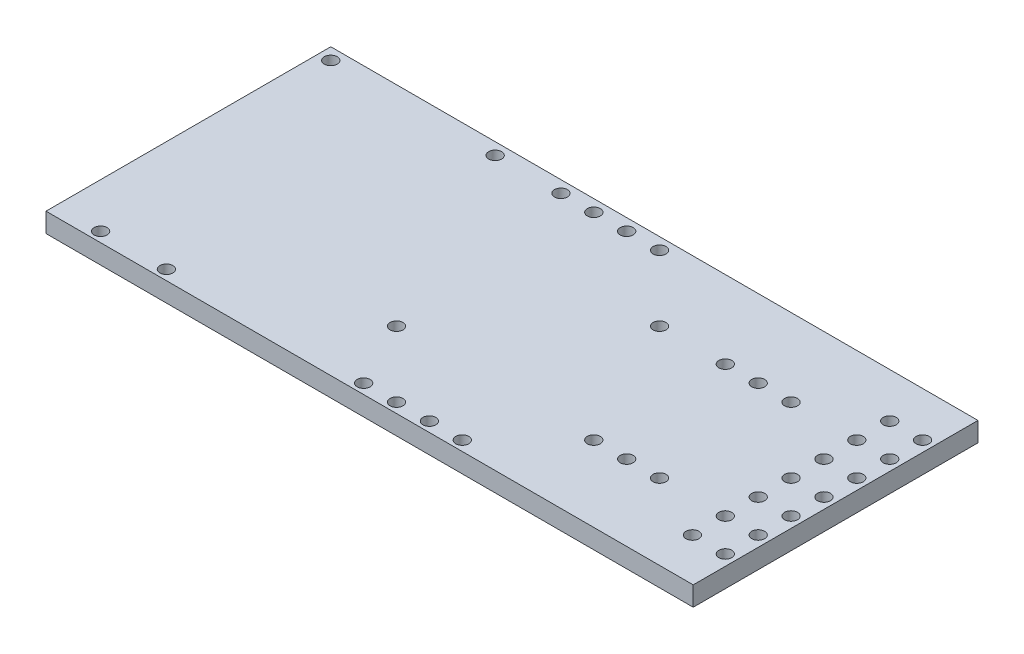
SolidWorks part; units mm, degrees
material "Chrome Stainless Steel"
ref_plane "Front Plane" through (0, 0, 0) normal (0, 0, 1) x (1, 0, 0)
ref_plane "Top Plane" through (0, 0, 0) normal (0, 1, 0) x (1, 0, 0)
ref_plane "Right Plane" through (0, 0, 0) normal (1, 0, 0) x (0, 0, -1)
sketch "Sketch1" plane through (0, 0, 0) normal (0, 1, 0) x (1, 0, 0)
  line L0 (0, 0) -> (2.54, 0) construction
  line L1 (-5.75, 3.5) -> (64.25, 3.5)
  line L2 (-5.75, 3.5) -> (-5.75, -26.5)
  line L3 (-5.75, -26.5) -> (64.25, -26.5)
  line L4 (64.25, 3.5) -> (64.25, -26.5)
  line L5 (0, 0) -> (0, -2.54) construction
  circle A0 centre (0, 0) radius 0.5 construction
  circle A1 centre (2.54, 0) radius 0.5 construction
  circle A2 centre (5.08, 0) radius 0.5 construction
  circle A3 centre (7.62, 0) radius 0.5 construction
  circle A4 centre (10.16, 0) radius 0.5 construction
  circle A5 centre (12.7, 0) radius 0.5 construction
  circle A6 centre (15.24, 0) radius 0.5 construction
  circle A7 centre (17.78, 0) radius 0.5 construction
  circle A8 centre (20.32, 0) radius 0.5 construction
  circle A9 centre (22.86, 0) radius 0.5 construction
  circle A10 centre (25.4, 0) radius 0.5 construction
  circle A11 centre (27.94, 0) radius 0.5 construction
  circle A12 centre (30.48, 0) radius 0.5 construction
  circle A13 centre (33.02, 0) radius 0.5 construction
  circle A14 centre (35.56, 0) radius 0.5 construction
  circle A15 centre (38.1, 0) radius 0.5 construction
  circle A16 centre (40.64, 0) radius 0.5 construction
  circle A17 centre (43.18, 0) radius 0.5 construction
  circle A18 centre (45.72, 0) radius 0.5 construction
  circle A19 centre (48.26, 0) radius 0.5 construction
  circle A20 centre (50.8, 0) radius 0.5 construction
  circle A21 centre (53.34, 0) radius 0.5 construction
  circle A22 centre (55.88, 0) radius 0.5 construction
  circle A23 centre (58.42, 0) radius 0.5 construction
  circle A24 centre (2.54, -2.54) radius 0.5 construction
  circle A25 centre (5.08, -2.54) radius 0.5 construction
  circle A26 centre (7.62, -2.54) radius 0.5 construction
  circle A27 centre (10.16, -2.54) radius 0.5 construction
  circle A28 centre (12.7, -2.54) radius 0.5
  circle A29 centre (15.24, -2.54) radius 0.5 construction
  circle A30 centre (17.78, -2.54) radius 0.5
  circle A31 centre (20.32, -2.54) radius 0.5
  circle A32 centre (22.86, -2.54) radius 0.5
  circle A33 centre (25.4, -2.54) radius 0.5
  circle A34 centre (27.94, -2.54) radius 0.5 construction
  circle A35 centre (30.48, -2.54) radius 0.5 construction
  circle A36 centre (33.02, -2.54) radius 0.5 construction
  circle A37 centre (35.56, -2.54) radius 0.5 construction
  circle A38 centre (38.1, -2.54) radius 0.5 construction
  circle A39 centre (40.64, -2.54) radius 0.5 construction
  circle A40 centre (43.18, -2.54) radius 0.5 construction
  circle A41 centre (45.72, -2.54) radius 0.5 construction
  circle A42 centre (48.26, -2.54) radius 0.5 construction
  circle A43 centre (50.8, -2.54) radius 0.5 construction
  circle A44 centre (53.34, -2.54) radius 0.5 construction
  circle A45 centre (55.88, -2.54) radius 0.5 construction
  circle A46 centre (58.42, -2.54) radius 0.5 construction
  circle A47 centre (2.54, -5.08) radius 0.5 construction
  circle A48 centre (5.08, -5.08) radius 0.5 construction
  circle A49 centre (7.62, -5.08) radius 0.5 construction
  circle A50 centre (10.16, -5.08) radius 0.5 construction
  circle A51 centre (12.7, -5.08) radius 0.5 construction
  circle A52 centre (15.24, -5.08) radius 0.5 construction
  circle A53 centre (17.78, -5.08) radius 0.5 construction
  circle A54 centre (20.32, -5.08) radius 0.5 construction
  circle A55 centre (22.86, -5.08) radius 0.5 construction
  circle A56 centre (25.4, -5.08) radius 0.5 construction
  circle A57 centre (27.94, -5.08) radius 0.5 construction
  circle A58 centre (30.48, -5.08) radius 0.5 construction
  circle A59 centre (33.02, -5.08) radius 0.5 construction
  circle A60 centre (35.56, -5.08) radius 0.5 construction
  circle A61 centre (38.1, -5.08) radius 0.5 construction
  circle A62 centre (40.64, -5.08) radius 0.5 construction
  circle A63 centre (43.18, -5.08) radius 0.5 construction
  circle A64 centre (45.72, -5.08) radius 0.5
  circle A65 centre (48.26, -5.08) radius 0.5
  circle A66 centre (50.8, -5.08) radius 0.5 construction
  circle A67 centre (53.34, -5.08) radius 0.5 construction
  circle A68 centre (55.88, -5.08) radius 0.5 construction
  circle A69 centre (58.42, -5.08) radius 0.5 construction
  circle A70 centre (2.54, -7.62) radius 0.5 construction
  circle A71 centre (5.08, -7.62) radius 0.5 construction
  circle A72 centre (7.62, -7.62) radius 0.5 construction
  circle A73 centre (10.16, -7.62) radius 0.5 construction
  circle A74 centre (12.7, -7.62) radius 0.5 construction
  circle A75 centre (15.24, -7.62) radius 0.5 construction
  circle A76 centre (17.78, -7.62) radius 0.5 construction
  circle A77 centre (20.32, -7.62) radius 0.5 construction
  circle A78 centre (22.86, -7.62) radius 0.5 construction
  circle A79 centre (25.4, -7.62) radius 0.5 construction
  circle A80 centre (27.94, -7.62) radius 0.5 construction
  circle A81 centre (30.48, -7.62) radius 0.5
  circle A82 centre (33.02, -7.62) radius 0.5 construction
  circle A83 centre (35.56, -7.62) radius 0.5
  circle A84 centre (38.1, -7.62) radius 0.5
  circle A85 centre (40.64, -7.62) radius 0.5
  circle A86 centre (43.18, -7.62) radius 0.5 construction
  circle A87 centre (45.72, -7.62) radius 0.5
  circle A88 centre (48.26, -7.62) radius 0.5
  circle A89 centre (50.8, -7.62) radius 0.5 construction
  circle A90 centre (53.34, -7.62) radius 0.5 construction
  circle A91 centre (55.88, -7.62) radius 0.5 construction
  circle A92 centre (58.42, -7.62) radius 0.5 construction
  circle A93 centre (2.54, -10.16) radius 0.5 construction
  circle A94 centre (5.08, -10.16) radius 0.5 construction
  circle A95 centre (7.62, -10.16) radius 0.5 construction
  circle A96 centre (10.16, -10.16) radius 0.5 construction
  circle A97 centre (12.7, -10.16) radius 0.5 construction
  circle A98 centre (15.24, -10.16) radius 0.5 construction
  circle A99 centre (17.78, -10.16) radius 0.5 construction
  circle A100 centre (20.32, -10.16) radius 0.5 construction
  circle A101 centre (22.86, -10.16) radius 0.5 construction
  circle A102 centre (25.4, -10.16) radius 0.5 construction
  circle A103 centre (27.94, -10.16) radius 0.5 construction
  circle A104 centre (30.48, -10.16) radius 0.5 construction
  circle A105 centre (33.02, -10.16) radius 0.5 construction
  circle A106 centre (35.56, -10.16) radius 0.5 construction
  circle A107 centre (38.1, -10.16) radius 0.5 construction
  circle A108 centre (40.64, -10.16) radius 0.5 construction
  circle A109 centre (43.18, -10.16) radius 0.5 construction
  circle A110 centre (45.72, -10.16) radius 0.5
  circle A111 centre (48.26, -10.16) radius 0.5
  circle A112 centre (50.8, -10.16) radius 0.5 construction
  circle A113 centre (53.34, -10.16) radius 0.5 construction
  circle A114 centre (55.88, -10.16) radius 0.5 construction
  circle A115 centre (58.42, -10.16) radius 0.5 construction
  circle A116 centre (2.54, -12.7) radius 0.5 construction
  circle A117 centre (5.08, -12.7) radius 0.5 construction
  circle A118 centre (7.62, -12.7) radius 0.5 construction
  circle A119 centre (10.16, -12.7) radius 0.5 construction
  circle A120 centre (12.7, -12.7) radius 0.5 construction
  circle A121 centre (15.24, -12.7) radius 0.5 construction
  circle A122 centre (17.78, -12.7) radius 0.5 construction
  circle A123 centre (20.32, -12.7) radius 0.5 construction
  circle A124 centre (22.86, -12.7) radius 0.5 construction
  circle A125 centre (25.4, -12.7) radius 0.5 construction
  circle A126 centre (27.94, -12.7) radius 0.5 construction
  circle A127 centre (30.48, -12.7) radius 0.5 construction
  circle A128 centre (33.02, -12.7) radius 0.5 construction
  circle A129 centre (35.56, -12.7) radius 0.5 construction
  circle A130 centre (38.1, -12.7) radius 0.5 construction
  circle A131 centre (40.64, -12.7) radius 0.5 construction
  circle A132 centre (43.18, -12.7) radius 0.5 construction
  circle A133 centre (45.72, -12.7) radius 0.5
  circle A134 centre (48.26, -12.7) radius 0.5
  circle A135 centre (50.8, -12.7) radius 0.5 construction
  circle A136 centre (53.34, -12.7) radius 0.5 construction
  circle A137 centre (55.88, -12.7) radius 0.5 construction
  circle A138 centre (58.42, -12.7) radius 0.5 construction
  circle A139 centre (2.54, -15.24) radius 0.5 construction
  circle A140 centre (5.08, -15.24) radius 0.5 construction
  circle A141 centre (7.62, -15.24) radius 0.5 construction
  circle A142 centre (10.16, -15.24) radius 0.5 construction
  circle A143 centre (12.7, -15.24) radius 0.5 construction
  circle A144 centre (15.24, -15.24) radius 0.5 construction
  circle A145 centre (17.78, -15.24) radius 0.5 construction
  circle A146 centre (20.32, -15.24) radius 0.5 construction
  circle A147 centre (22.86, -15.24) radius 0.5 construction
  circle A148 centre (25.4, -15.24) radius 0.5 construction
  circle A149 centre (27.94, -15.24) radius 0.5 construction
  circle A150 centre (30.48, -15.24) radius 0.5 construction
  circle A151 centre (33.02, -15.24) radius 0.5 construction
  circle A152 centre (35.56, -15.24) radius 0.5 construction
  circle A153 centre (38.1, -15.24) radius 0.5 construction
  circle A154 centre (40.64, -15.24) radius 0.5 construction
  circle A155 centre (43.18, -15.24) radius 0.5 construction
  circle A156 centre (45.72, -15.24) radius 0.5
  circle A157 centre (48.26, -15.24) radius 0.5
  circle A158 centre (50.8, -15.24) radius 0.5 construction
  circle A159 centre (53.34, -15.24) radius 0.5 construction
  circle A160 centre (55.88, -15.24) radius 0.5 construction
  circle A161 centre (58.42, -15.24) radius 0.5 construction
  circle A162 centre (2.54, -17.78) radius 0.5 construction
  circle A163 centre (5.08, -17.78) radius 0.5 construction
  circle A164 centre (7.62, -17.78) radius 0.5 construction
  circle A165 centre (10.16, -17.78) radius 0.5 construction
  circle A166 centre (12.7, -17.78) radius 0.5 construction
  circle A167 centre (15.24, -17.78) radius 0.5 construction
  circle A168 centre (17.78, -17.78) radius 0.5 construction
  circle A169 centre (20.32, -17.78) radius 0.5
  circle A170 centre (22.86, -17.78) radius 0.5 construction
  circle A171 centre (25.4, -17.78) radius 0.5 construction
  circle A172 centre (27.94, -17.78) radius 0.5 construction
  circle A173 centre (30.48, -17.78) radius 0.5 construction
  circle A174 centre (33.02, -17.78) radius 0.5 construction
  circle A175 centre (35.56, -17.78) radius 0.5
  circle A176 centre (38.1, -17.78) radius 0.5
  circle A177 centre (40.64, -17.78) radius 0.5
  circle A178 centre (43.18, -17.78) radius 0.5 construction
  circle A179 centre (45.72, -17.78) radius 0.5
  circle A180 centre (48.26, -17.78) radius 0.5
  circle A181 centre (50.8, -17.78) radius 0.5 construction
  circle A182 centre (53.34, -17.78) radius 0.5 construction
  circle A183 centre (55.88, -17.78) radius 0.5 construction
  circle A184 centre (58.42, -17.78) radius 0.5 construction
  circle A185 centre (2.54, -20.32) radius 0.5 construction
  circle A186 centre (5.08, -20.32) radius 0.5 construction
  circle A187 centre (7.62, -20.32) radius 0.5 construction
  circle A188 centre (10.16, -20.32) radius 0.5 construction
  circle A189 centre (12.7, -20.32) radius 0.5 construction
  circle A190 centre (15.24, -20.32) radius 0.5 construction
  circle A191 centre (17.78, -20.32) radius 0.5 construction
  circle A192 centre (20.32, -20.32) radius 0.5 construction
  circle A193 centre (62.25, 1.5) radius 1
  circle A194 centre (62.25, -24.5) radius 1
  circle A195 centre (-3.75, -24.5) radius 1
  circle A196 centre (-3.75, 1.5) radius 1
  circle A197 centre (22.86, -20.32) radius 0.5 construction
  circle A198 centre (25.4, -20.32) radius 0.5 construction
  circle A199 centre (27.94, -20.32) radius 0.5 construction
  circle A200 centre (30.48, -20.32) radius 0.5 construction
  circle A201 centre (33.02, -20.32) radius 0.5 construction
  circle A202 centre (35.56, -20.32) radius 0.5 construction
  circle A203 centre (38.1, -20.32) radius 0.5 construction
  circle A204 centre (40.64, -20.32) radius 0.5 construction
  circle A205 centre (43.18, -20.32) radius 0.5 construction
  circle A206 centre (45.72, -20.32) radius 0.5
  circle A207 centre (48.26, -20.32) radius 0.5
  circle A208 centre (50.8, -20.32) radius 0.5 construction
  circle A209 centre (53.34, -20.32) radius 0.5 construction
  circle A210 centre (55.88, -20.32) radius 0.5 construction
  circle A211 centre (58.42, -20.32) radius 0.5 construction
  circle A212 centre (2.54, -22.86) radius 0.5
  circle A213 centre (5.08, -22.86) radius 0.5 construction
  circle A214 centre (7.62, -22.86) radius 0.5
  circle A215 centre (10.16, -22.86) radius 0.5 construction
  circle A216 centre (12.7, -22.86) radius 0.5 construction
  circle A217 centre (15.24, -22.86) radius 0.5 construction
  circle A218 centre (17.78, -22.86) radius 0.5 construction
  circle A219 centre (20.32, -22.86) radius 0.5 construction
  circle A220 centre (22.86, -22.86) radius 0.5
  circle A221 centre (25.4, -22.86) radius 0.5
  circle A222 centre (27.94, -22.86) radius 0.5
  circle A223 centre (30.48, -22.86) radius 0.5
  circle A224 centre (33.02, -22.86) radius 0.5 construction
  circle A225 centre (35.56, -22.86) radius 0.5 construction
  circle A226 centre (38.1, -22.86) radius 0.5 construction
  circle A227 centre (40.64, -22.86) radius 0.5 construction
  circle A228 centre (43.18, -22.86) radius 0.5 construction
  circle A229 centre (45.72, -22.86) radius 0.5 construction
  circle A230 centre (48.26, -22.86) radius 0.5 construction
  circle A231 centre (50.8, -22.86) radius 0.5 construction
  circle A232 centre (53.34, -22.86) radius 0.5 construction
  circle A233 centre (55.88, -22.86) radius 0.5 construction
  circle A234 centre (58.42, -22.86) radius 0.5 construction
  circle A235 centre (0, -2.54) radius 0.5
  circle A236 centre (0, -5.08) radius 0.5 construction
  circle A237 centre (0, -7.62) radius 0.5 construction
  circle A238 centre (0, -10.16) radius 0.5 construction
  circle A239 centre (0, -12.7) radius 0.5 construction
  circle A240 centre (0, -15.24) radius 0.5 construction
  circle A241 centre (0, -17.78) radius 0.5 construction
  circle A242 centre (0, -20.32) radius 0.5 construction
  circle A243 centre (0, -22.86) radius 0.5 construction
  dimension "D1" = 70
  dimension "D2" = 1
  dimension "D4" = 30
  dimension "D5" = 2
  dimension "D7" = 1
  dimension "D8" = 1
  dimension "D9" = 1
  dimension "D10" = 1
  dimension "D11" = 3.5
  dimension "D12" = 5.75
  dimension "D14" = 2.54
  dimension "D15" = 2.54
  dimension "D3" = 24
  dimension "D6" = 10
other "AlignGroup1"
other "AlignGroup2"
extrude "Boss-Extrude1" add sketch "Sketch1" along normal blind 1.5
sketch "Sketch2" plane through (0, 1.5, 0) normal (0, 1, 0) x (1, 0, 0)
  line L0 (-3.75, -25.5) -> (62.25, -25.5) construction
  line L1 (-5.75, -26.5) -> (64.25, -26.5) construction
  line L2 (-2.75, -24.5) -> (-2.75, 1.5) construction
  line L3 (-1.75, 1.5) -> (-1.75, -24.5) construction
  line L4 (-5.75, 3.5) -> (-5.75, -26.5) construction
  circle A0 centre (-3.75, -24.5) radius 1 construction
  circle A1 centre (62.25, -24.5) radius 1 construction
  circle A2 centre (-3.75, 1.5) radius 1 construction
  text T0 "A B C D E F G H I J K L M N O P Q R S T U V W X\r\n" font "Consolas" height 1
  text T1 "01 02 03 04 05 06 07 08 09 10" font "Century Gothic" height 1
  dimension "D2" = 3
  dimension "D1" = 1
  dimension "D3" = 1
extrude "Cut-Extrude1" cut sketch "Sketch2" against normal blind 0.5
sketch "LCD PINS" [suppressed] plane through (0, 0, 0) normal (0, -1, 0) x (1, 0, 0)
  text T0 "          RST" font "Consolas" height 0.5
  text T1 "          CE" font "Consolas" height 0.5
  text T2 "          DC" font "Consolas" height 0.5
  text T3 "          DIN" font "Consolas" height 0.5
  text T4 "          CLK" font "Consolas" height 0.5
  text T5 "          VCC" font "Consolas" height 0.5
  text T6 "         LIGHT" font "Consolas" height 0.5
  text T7 "          GND" font "Consolas" height 0.5
sketch "Sketch3" plane through (0, 1.5, 0) normal (0, 1, 0) x (1, 0, 0)
  line L0 (64.25, -26.5) -> (64.25, 3.5) construction
  line L1 (-0.915, -1.6238) -> (49.085, -1.6238)
  line L2 (-0.915, -1.6238) -> (-0.915, -23.6238)
  line L3 (-0.915, -23.6238) -> (49.085, -23.6238)
  line L4 (49.085, -1.6238) -> (49.085, -23.6238)
  line L5 (64.25, 3.5) -> (-5.75, 3.5) construction
  line L6 (-5.75, -26.5) -> (64.25, -26.5) construction
  line L7 (-5.75, 3.5) -> (-5.75, -26.5) construction
  line L8 (64.25, -26.5) -> (64.25, 3.5)
  line L9 (64.25, 3.5) -> (-5.75, 3.5)
  line L10 (-5.75, -26.5) -> (64.25, -26.5)
  line L11 (-5.75, 3.5) -> (-5.75, -26.5)
  dimension "D1" = 50
  dimension "D2" = 22
extrude "Cut-Extrude2" cut sketch "Sketch3" against normal through all both and the other way through all
